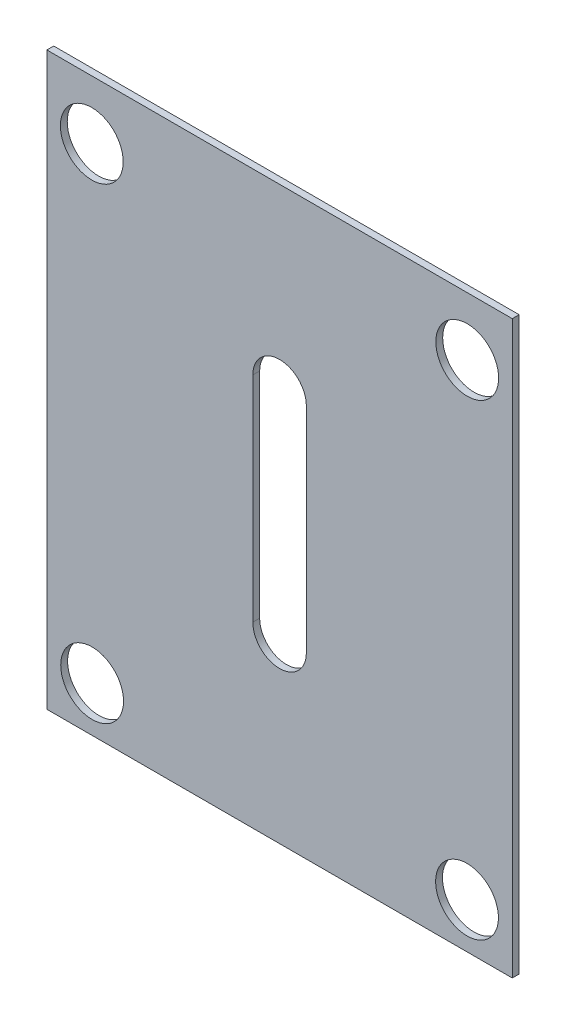
SolidWorks part; units mm, degrees
material "1060 Alloy"
ref_plane "Front Plane" through (0, 0, 0) normal (0, 0, 1) x (1, 0, 0)
ref_plane "Top Plane" through (0, 0, 0) normal (0, 1, 0) x (1, 0, 0)
ref_plane "Right Plane" through (0, 0, 0) normal (1, 0, 0) x (0, 0, -1)
sketch "Sketch1" plane through (0, 0, 0) normal (0, 0, 1) x (1, 0, 0)
  line L1 (-4656.6619, -4345.8581) -> (-4615.2619, -4345.8581)
  line L2 (-4656.6619, -4345.8581) -> (-4656.6619, -4396.6581)
  line L3 (-4656.6619, -4396.6581) -> (-4615.2619, -4396.6581)
  line L4 (-4615.2619, -4345.8581) -> (-4615.2619, -4396.6581)
  dimension "D1" = 50.8
  dimension "D2" = 41.4
extrude "Boss-Extrude1" add sketch "Sketch1" along normal blind 0.6096
sketch "Sketch4" plane through (0, 0, 0.6096) normal (0, 0, 1) x (1, 0, 0)
  line L0 (-4635.9619, -4380.7831) -> (-4635.9619, -4361.7331) construction
  line L1 (-4638.3432, -4380.7831) -> (-4638.3432, -4361.7331)
  line L2 (-4633.5807, -4380.7831) -> (-4633.5807, -4361.7331)
  line L3 (-4635.9619, -4345.8581) -> (-4635.9619, -4396.6581) construction
  line L4 (-4615.2619, -4345.8581) -> (-4656.6619, -4345.8581) construction
  line L5 (-4656.6619, -4396.6581) -> (-4615.2619, -4396.6581) construction
  line L6 (-4635.9619, -4371.2581) -> (-4615.2619, -4371.2581) construction
  line L10 (-4615.2619, -4396.6581) -> (-4615.2619, -4345.8581) construction
  line L11 (-4635.9619, -4371.2581) -> (-4656.6619, -4371.2581) construction
  line L12 (-4656.6619, -4345.8581) -> (-4656.6619, -4396.6581) construction
  arc A0 (-4638.3432, -4380.7831) -> (-4633.5807, -4380.7831) centre (-4635.9619, -4380.7831) ccw
  arc A1 (-4633.5807, -4361.7331) -> (-4638.3432, -4361.7331) centre (-4635.9619, -4361.7331) ccw
  point P2 (-4635.9619, -4371.2581)
  dimension "D1" = 2.3813
  dimension "D2" = 19.05
extrude "Cut-Extrude2" cut sketch "Sketch4" against normal up to surface (0.6096 mm away) up to face at (-4635.9619, -4371.2581, 0)
sketch "Sketch9" plane through (0, 0, 0) normal (0, 0, -1) x (-1, 0, 0)
  line L0 (4619.2859, -4392.6341) -> (4619.2859, -4396.6581) construction
  line L2 (4615.2619, -4396.6581) -> (4615.2619, -4345.8581) construction
  line L4 (4656.6619, -4345.8581) -> (4656.6619, -4396.6581) construction
  line L5 (4619.2859, -4392.6341) -> (4615.2619, -4392.6341) construction
  line L6 (4652.638, -4392.6341) -> (4656.6619, -4392.6341) construction
  line L7 (4656.6619, -4396.6581) -> (4615.2619, -4396.6581) construction
  line L11 (4652.638, -4392.6341) -> (4652.638, -4396.6581) construction
  circle A5 centre (4619.2672, -4351.0441) radius 2.794
  circle A6 centre (4652.6672, -4351.0889) radius 2.794
  circle A7 centre (4619.2859, -4392.6341) radius 2.794
  circle A8 centre (4652.638, -4392.6341) radius 2.794
extrude "Cut-Extrude3" cut sketch "Sketch9" against normal up to surface (0.6096 mm away) up to face at (-4635.9619, -4371.2581, 0.6096)
sketch "Sketch10" plane through (0, 0, 0) normal (0, 0, -1) x (-1, 0, 0)
  line L0 (4638.3432, -4380.7831) -> (4638.3432, -4361.7331) construction
  point P8 (4635.9619, -4371.2581)
  dimension "D1" = 2.3813
  dimension "D2" = 9.525
